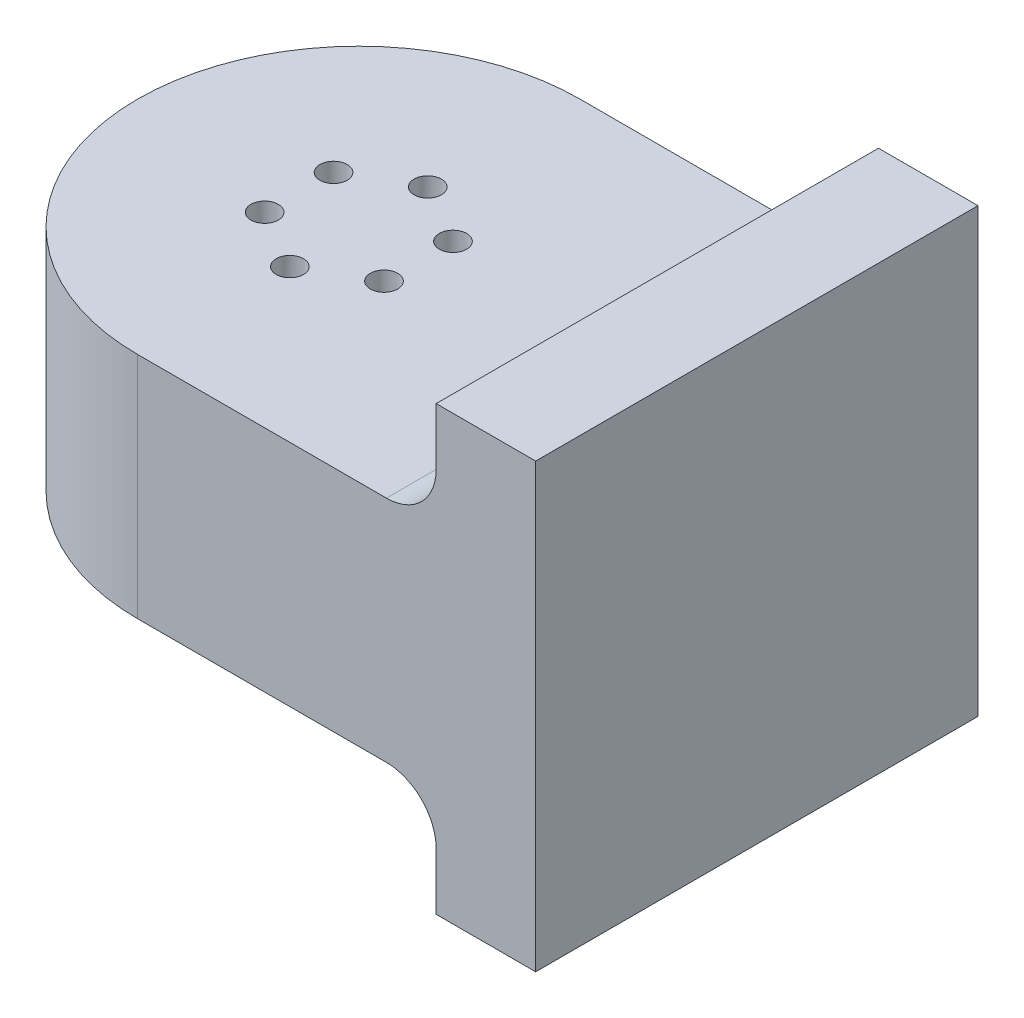
SolidWorks part; units mm, degrees
ref_plane "Front Plane" through (0, 0, 0) normal (0, 0, 1) x (1, 0, 0)
ref_plane "Top Plane" through (0, 0, 0) normal (0, 1, 0) x (1, 0, 0)
ref_plane "Right Plane" through (0, 0, 0) normal (1, 0, 0) x (0, 0, -1)
sketch "Sketch1" plane through (0, 0, 0) normal (0, 1, 0) x (1, 0, 0)
  line L0 (0, 44.45) -> (60, 44.45)
  line L1 (60, 44.45) -> (60, -44.45)
  line L2 (60, -44.45) -> (0, -44.45)
  arc A0 (0, 44.45) -> (0, -44.45) centre (0, 0) ccw
  dimension "D1" = 44.45
  dimension "D2" = 60
extrude "Boss-Extrude1" add sketch "Sketch1" along normal blind 46
sketch "Sketch2" plane through (0, 0, 0) normal (0, -1, 0) x (-1, 0, 0)
  line L1 (0, -13.8564) -> (12, -6.9282)
  line L2 (12, -6.9282) -> (12, 6.9282)
  line L3 (12, 6.9282) -> (0, 13.8564)
  line L4 (0, 13.8564) -> (-12, 6.9282)
  line L5 (-12, 6.9282) -> (-12, -6.9282)
  line L6 (-12, -6.9282) -> (0, -13.8564)
  circle A0 centre (0, 0) radius 12 construction
  circle A1 centre (0, -13.8564) radius 2.75
  circle A2 centre (12, -6.9282) radius 2.75
  circle A3 centre (12, 6.9282) radius 2.75
  circle A4 centre (0, 13.8564) radius 2.75
  circle A5 centre (-12, 6.9282) radius 2.75
  circle A6 centre (-12, -6.9282) radius 2.75
extrude "Cut-Extrude2" cut sketch "Sketch2" against normal blind 76 contours L6 A1 L1 | L5 A6 L6 | L4 A5 L5 | L3 A4 L4 | L2 A3 L3 | L1 A2 L2 | L2 A2 L1 | L1 A1 L6 | L6 A6 L5 | L5 A5 L4 | L4 A4 L3 | L3 A3 L2 region at (0, 0, 12.3403) region at (0, 0, 14.6145) region at (-10.687, 0, 6.1701) region at (-12.6565, 0, 7.3072) region at (12.6565, 0, 7.3072) region at (10.687, 0, 6.1701) region at (-10.687, 0, -6.1701) region at (-12.6565, 0, -7.3072) region at (12.6565, 0, -7.3072) region at (10.687, 0, -6.1701) region at (0, 0, -12.3403) region at (0, 0, -14.6145)
sketch "Sketch3" plane through (60, 0, 0) normal (1, 0, 0) x (0, 0, -1)
  line L2 (-44.45, 67.45) -> (-44.45, -21.45)
  line L4 (-44.45, 67.45) -> (44.45, 67.45)
  line L5 (44.45, 67.45) -> (44.45, -21.45)
  line L6 (-44.45, -21.45) -> (44.45, -21.45)
  dimension "D1" = 88.9
  dimension "D2" = 88.9
extrude "Boss-Extrude2" add sketch "Sketch3" along normal blind 20
fillet "Fillet1" radius 10 2 edges at (60, 46, 0) (60, 0, 0)
